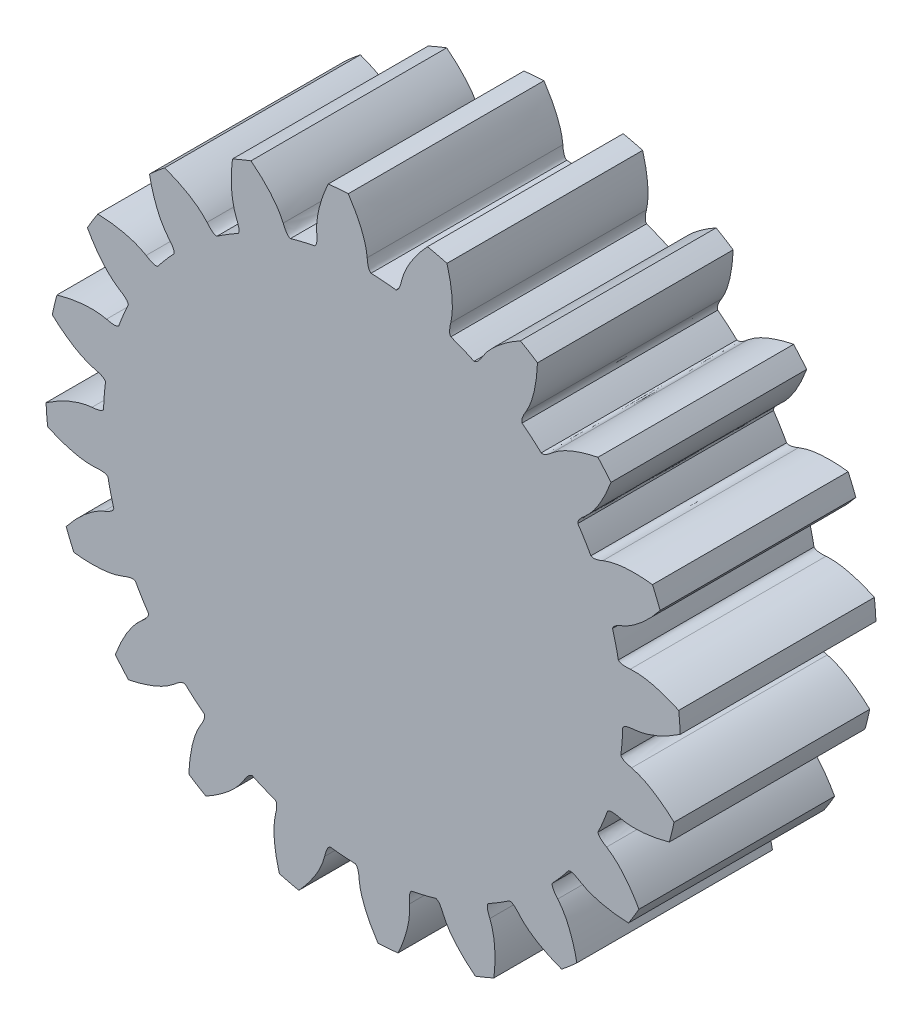
SolidWorks part; units mm, degrees
ref_plane "Front Plane" through (0, 0, 0) normal (0, 0, 1) x (1, 0, 0)
ref_plane "Top Plane" through (0, 0, 0) normal (0, 1, 0) x (1, 0, 0)
ref_plane "Right Plane" through (0, 0, 0) normal (1, 0, 0) x (0, 0, -1)
sketch "involute" plane through (0, 0, 0) normal (0, 0, 1) x (1, 0, 0)
  line L0 (0, 0) -> (0, 12.7) construction
  line L1 (0, 0) -> (-4.0817, 11.2144) construction
  line L2 (-4.0817, 11.2144) -> (0, 12.7) construction
  line L3 (-6.6755, 9.8925) -> (-0.6557, 13.9546) construction
  line L4 (-5.977, 10.3295) -> (-0.4046, 13.5539) construction
  line L5 (-5.14, 10.7705) -> (-0.1837, 13.1357) construction
  line L6 (0, 12.7) -> (-0.1837, 13.1357) construction
  line L7 (-0.1837, 13.1357) -> (-0.4046, 13.5539) construction
  line L8 (-0.4046, 13.5539) -> (-0.6557, 13.9546) construction
  circle A0 centre (0, 0) radius 12.7 construction
  arc A1 (0.1779, 11.9328) -> (-6.6755, 9.8925) centre (0, 0) ccw construction
  circle A2 centre (0, 0) radius 13.97 construction
  arc A3 (-4.0817, 11.2144) -> (0.1779, 11.9328) centre (0, 0) cw construction
  arc A4 (0.1779, 11.9328) -> (-5.977, 10.3295) centre (0, 0) ccw construction
  arc A5 (0.1779, 11.9328) -> (-5.14, 10.7705) centre (0, 0) ccw construction
  point P15 (-7.1609, 9.5469)
  dimension "D1" = 25.4
  dimension "D4" = 27.94
  dimension "D2" = 20
sketch "undercut" plane through (0, 0, 0) normal (0, 0, 1) x (1, 0, 0)
  line L0 (0.1779, 11.9328) -> (0.3455, 11.4248) construction
  line L1 (-7.683, 11.6676) -> (8.3741, 11.1819) construction
  line L2 (0.1779, 11.9328) -> (0.1892, 11.7957) construction
  line L3 (-4.7423, 13.1405) -> (10.7562, 8.9143) construction
  line L4 (-6.1616, 12.5378) -> (9.7083, 10.0454) construction
  line L5 (0.2567, 11.5298) -> (0.1779, 11.9328) construction
  line L6 (0.3455, 11.4248) -> (0.2567, 11.5298) construction
  line L7 (10.3167, 9.4195) -> (-5.3665, 12.8981) construction
  line L8 (0.2137, 11.6604) -> (0.1779, 11.9328) construction
  line L9 (0.2137, 11.6604) -> (0.2567, 11.5298) construction
  line L10 (0.1892, 11.7957) -> (0.2137, 11.6604) construction
  circle A0 centre (0, 0) radius 13.97 construction
  dimension "D1" = 70
  dimension "D2" = 11.43
  dimension "D3" = 70
  dimension "D4" = 11.43
  dimension "D5" = 70
  dimension "D6" = 11.43
  dimension "D7" = 70
  dimension "D8" = 11.43
sketch "Sketch2" plane through (0, 0, 0) normal (0, 0, 1) x (1, 0, 0)
  circle A0 centre (0, 0) radius 13.97
extrude "Boss-Extrude1" add sketch "Sketch2" along normal mid plane 8.6114
sketch "Sketch3" plane through (0, 0, 4.3057) normal (0, 0, 1) x (1, 0, 0)
  line L0 (0, 12.7) -> (0, 0) construction
  line L1 (0, 0) -> (0.8968, 11.3948) construction
  arc A0 (0.3455, 11.4248) -> (1.4459, 11.3382) centre (0, 0) cw
  arc A1 (-0.6557, 13.9546) -> (2.8306, 13.6802) centre (0, 0) cw
  spline S0 degree 3 poles (-0.6557, 13.9546) (-0.4792, 13.6933) (-0.1076, 13.0565) (0.138, 12.3566) (0.1779, 11.9328) knots 0 0 0 0 0.428684 1 1 1 1
  spline S1 degree 3 poles (0.1779, 11.9328) (0.1811, 11.8405) (0.2049, 11.6602) (0.2639, 11.4806) (0.3455, 11.4248) knots 0 0 0 0 0.5 1 1 1 1
  spline S2 degree 3 poles (2.8306, 13.6802) (2.6154, 13.4497) (2.1487, 12.879) (1.7967, 12.2261) (1.691, 11.8137) knots 0 0 0 0 0.428684 1 1 1 1
  spline S3 degree 3 poles (1.691, 11.8137) (1.6734, 11.7231) (1.6217, 11.5487) (1.5354, 11.3805) (1.4459, 11.3382) knots 0 0 0 0 0.5 1 1 1 1
  dimension "D1" = 4.5
extrude "Cut-Extrude1" cut sketch "Sketch3" against normal through all both and the other way through all
pattern_circular "CirPattern1" count 20 over 360 about axis through (0, 0, 4.3057) along (0, 0, -1) of "Cut-Extrude1"
sketch "Sketch4" plane through (0, 0, 4.3057) normal (0, 0, 1) x (1, 0, 0)
  line L0 (0, 0) -> (0.9363, 11.8973) construction
  line L2 (0, 0) -> (0, 12.7) construction
  arc A0 (0.1779, 11.9328) -> (1.691, 11.8137) centre (0, 0) cw
  arc A1 (-0.6557, 13.9546) -> (2.8306, 13.6802) centre (0, 0) cw
  spline S0 degree 3 poles (-0.6557, 13.9546) (-0.4792, 13.6933) (-0.1076, 13.0565) (0.138, 12.3566) (0.1779, 11.9328) knots 0 0 0 0 0.428684 1 1 1 1
  spline S1 degree 3 poles (2.8306, 13.6802) (2.6154, 13.4497) (2.1487, 12.879) (1.7967, 12.2261) (1.691, 11.8137) knots 0 0 0 0 0.428684 1 1 1 1
  point P21 (0, 0)
  point P22 (0, 0)
  dimension "D1" = 4.5
extrude "Cut-Extrude2" [suppressed] cut sketch "Sketch4" against normal through all
pattern_circular "CirPattern2" [suppressed] count 60 over 360 of bodies 104
equation "\"n\" = 20"
equation "\"dp\"= 20"
equation "\"a\"= 20"
equation "\"m\"= 1 / \"dp\""
equation "\"pd\"= \"n\" / \"dp\""
equation "\"add\"= \"m\""
equation "\"ded\"= 1.25 * \"m\""
equation "\"od\"= \"pd\" + 2 * \"add\""
equation "\"rd\"= \"pd\" - 2 * \"add\""
equation "\"D1@involute\" = \"pd\""
equation "\"D2@involute\" = \"a\""
equation "\"D4@involute\" = \"od\""
equation "\"D1@undercut\" = 90 - \"a\""
equation "\"D2@undercut\" = \"rd\" / 2"
equation "\"D3@undercut\" = 90 - \"a\""
equation "\"D4@undercut\" = \"D2@undercut\""
equation "\"D5@undercut\" = \"D3@undercut\""
equation "\"D6@undercut\" = \"D2@undercut\""
equation "\"D7@undercut\" = \"D3@undercut\""
equation "\"D8@undercut\" = \"D2@undercut\""
equation "\"D1@Sketch3\"=90/\"n\""
equation "\"D1@CirPattern1\"=\"n\""
equation "\"D1@Sketch4\"=90/\"n\""
equation "\"Cut-Extrude2\"= iif ( \"n\" <= 5 / ( 2 - 2 * cos ( \"a\" ) ) , \"suppressed\" , \"unsuppressed\" )"
equation "\"undercut\" = IIF ( \"n\" < 5 / ( 2 - 2 * cos ( \"a\" ) ) , \"unsuppressed\" , \"suppressed\" )"
equation "\"CirPattern2\"= iif ( \"n\" <= 5 / ( 2 - 2 * cos ( \"a\" ) ) , \"suppressed\" , \"unsuppressed\" )"
equation "\"CirPattern1\"= IIF ( \"n\" < 5 / ( 2 - 2 * cos ( \"a\" ) ) , \"unsuppressed\" , \"suppressed\" )"
equation "\"Cut-Extrude1\"= IIF ( \"n\" < 5 / ( 2 - 2 * cos ( \"a\" ) ) , \"unsuppressed\" , \"suppressed\" )"
